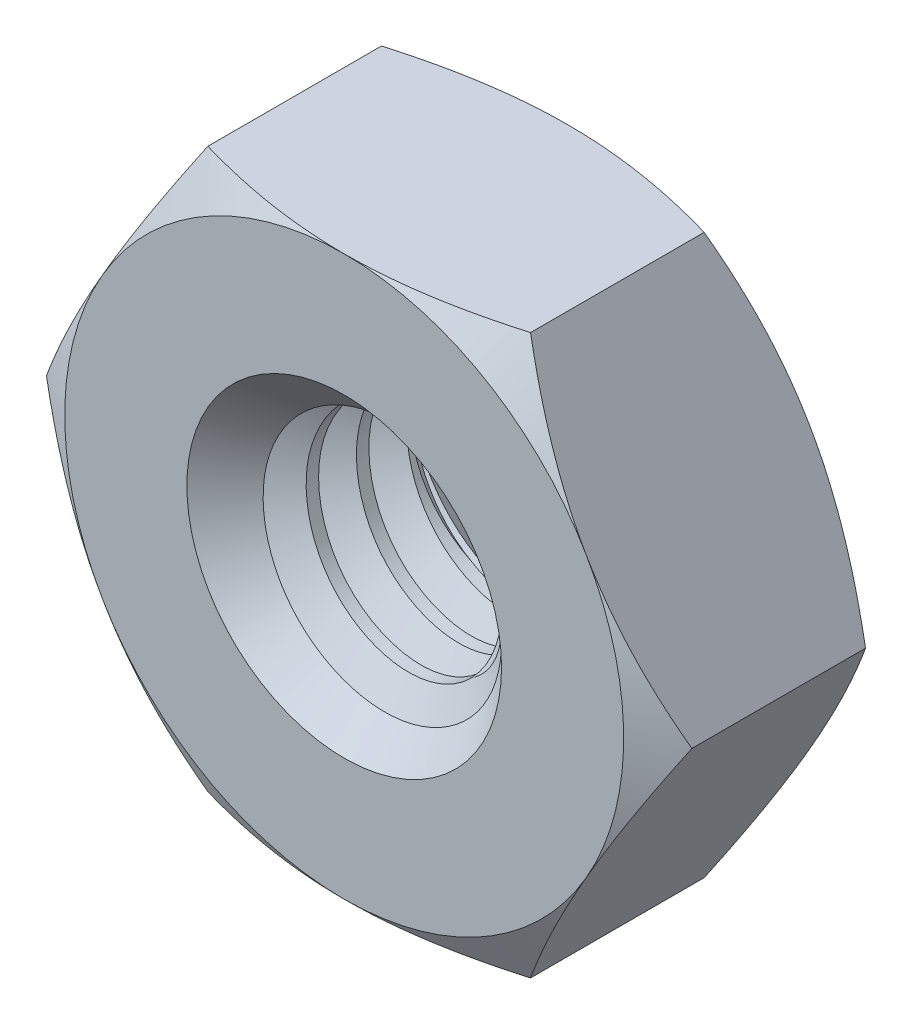
SolidWorks part; units mm, degrees
ref_plane "Front" through (0, 0, 0) normal (0, 0, 1) x (1, 0, 0)
ref_plane "Top" through (0, 0, 0) normal (0, 1, 0) x (1, 0, 0)
ref_plane "Right" through (0, 0, 0) normal (1, 0, 0) x (0, 0, -1)
sketch "Çizim1" plane through (0, 0, 0) normal (0, 0, 1) x (1, 0, 0)
  line L1 (2.8868, 0) -> (1.4434, 2.5)
  line L2 (1.4434, 2.5) -> (-1.4434, 2.5)
  line L3 (-1.4434, 2.5) -> (-2.8868, 0)
  line L4 (-2.8868, 0) -> (-1.4434, -2.5)
  line L5 (-1.4434, -2.5) -> (1.4434, -2.5)
  line L6 (1.4434, -2.5) -> (2.8868, 0)
  circle A0 centre (0, 0) radius 2.5 construction
  dimension "D1" = 5
extrude "Yükseklik-Ekstrüzyon1" add sketch "Çizim1" along normal blind 2
sketch "Çizim2" plane through (0, 0, 2) normal (0, 0, 1) x (1, 0, 0)
  circle A0 centre (0, 0) radius 2.5
extrude "Kes-Ekstrüzyon1" cut sketch "Çizim2" against normal blind 2 draft 60 flip side to cut
sketch "Çizim3" plane through (0, 0, 0) normal (0, 0, -1) x (-1, 0, 0)
  circle A0 centre (0, 0) radius 2.5
extrude "Kes-Ekstrüzyon2" cut sketch "Çizim3" against normal blind 2 draft 60 flip side to cut
sketch "Çizim4" plane through (0, 0, 2) normal (0, 0, 1) x (1, 0, 0)
  circle A0 centre (0, 0) radius 0.9575
  dimension "D1" = 1.915
extrude "Kes-Ekstrüzyon3" cut sketch "Çizim4" against normal blind 2
chamfer "Pah1" distance 0.45 angle 45 2 edges at (0.9575, 0, 0) (0.9575, 0, 2)
sketch "Çizim6" plane through (0, 0, 2) normal (0, 0, 1) x (1, 0, 0)
  circle A0 centre (0, 0) radius 0.9575
curve "Helis/Spiral1" pitch 0.45 height 3 radius 0.9575 centre (0, 0, 2) axis (0, 0, -1) start towards (-1, 0, 0)
ref_plane "Düzlem1" through (0.4787, -0.8292, -1) normal (-0.8636, -0.4986, -0.0746) x (-0.0646, -0.0373, 0.9972)
sketch "Çizim7" plane through (0.4787, -0.8292, -1) normal (-0.8636, -0.4986, -0.0746) x (-0.0646, -0.0373, 0.9972)
  line L0 (0.2159, 0.0814) -> (-0.2159, 0.0814)
  line L1 (0, -0.2925) -> (0.2159, 0.0814)
  line L3 (-0.2159, 0.0814) -> (0, -0.2925)
  line L5 (0, 0.1463) -> (-0.2533, 0.1462) [skipped]
  circle A0 centre (0, 0) radius 0.1463 construction
  dimension "D1" = 0.2925
sweep "Kes-Süpür1" cut profiles "Çizim7" path "Helis/Spiral1" align with end faces yes
